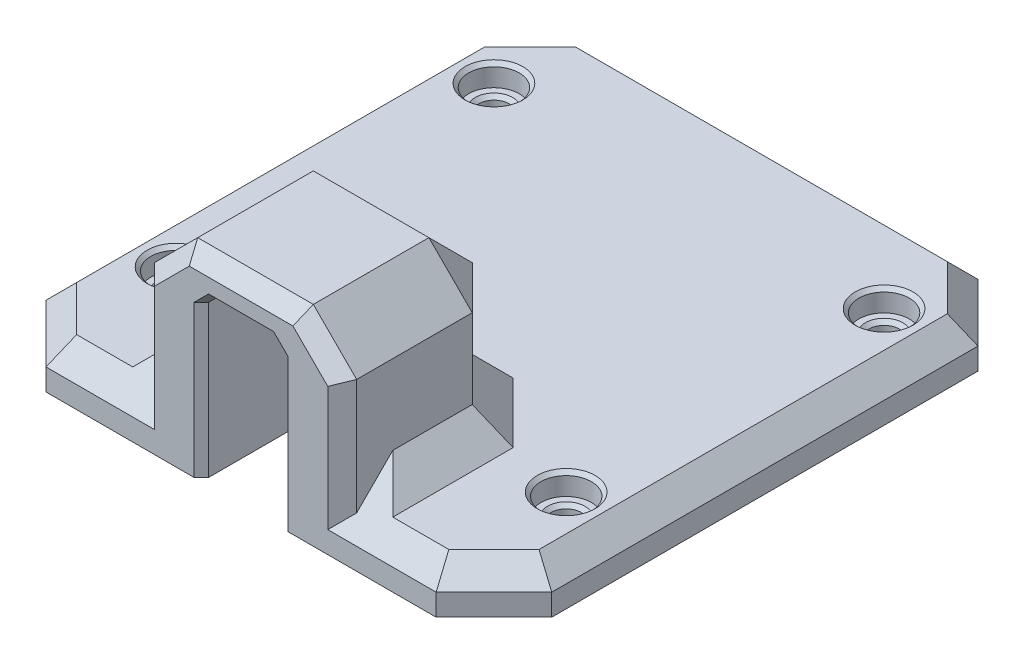
SolidWorks part; units mm, degrees
material "ABS"
ref_plane "Front Plane" through (0, 0, 0) normal (0, 0, 1) x (1, 0, 0)
ref_plane "Top Plane" through (0, 0, 0) normal (0, 1, 0) x (1, 0, 0)
ref_plane "Right Plane" through (0, 0, 0) normal (1, 0, 0) x (0, 0, -1)
sketch "Sketch1" plane through (0, 0, 0) normal (0, 1, 0) x (1, 0, 0)
  line L0 (-35, 27) -> (-27, 35)
  line L1 (-27, 35) -> (27, 35)
  line L2 (-35, 27) -> (-35, -32)
  line L4 (35, 27) -> (35, -32)
  line L5 (27, 35) -> (35, 27)
  line L6 (27, -40) -> (35, -32)
  line L7 (-35, -32) -> (-27, -40)
  line L8 (-1000, 0) -> (49000, 0) construction
  line L9 (0, -1000) -> (0, 49000) construction
  line L11 (-5, -40) -> (-5, -27.65) construction
  line L13 (5, -27.65) -> (5, -40) construction
  line L15 (-5.5, -40) -> (-5.5, -27.8571)
  line L17 (-5.5, -27.8571) -> (-9.5, -23.8571)
  line L18 (-5, -27.65) -> (-9, -23.65) construction
  line L19 (-9, -23.65) -> (-9, -21.15) construction
  line L20 (-9, -21.15) -> (9, -21.15) construction
  line L21 (9, -21.15) -> (9, -23.65) construction
  line L22 (9, -23.65) -> (5, -27.65) construction
  line L23 (-9.5, -23.8571) -> (-9.5, -20.65)
  line L24 (-9.5, -20.65) -> (9.5, -20.65)
  line L25 (9.5, -20.65) -> (9.5, -23.8571)
  line L26 (9.5, -23.8571) -> (5.5, -27.8571)
  line L27 (5.5, -27.8571) -> (5.5, -40)
  line L28 (-27, -40) -> (-5.5, -40)
  line L29 (5.5, -40) -> (27, -40)
  circle A0 centre (-27, 22) radius 2.1
  circle A1 centre (27, 22) radius 2.1
  circle A2 centre (27, -22) radius 2.1
  circle A3 centre (-27, -22) radius 2.1
  point P1 (0, 35)
  point P36 (0, -21.15)
  dimension "D7" = 4.2
  dimension "D1" = 75
  dimension "D2" = 70
  dimension "D3" = 35
  dimension "D4" = 8
  dimension "D5" = 27
  dimension "D6" = 22
  dimension "D8" = 18.85
  dimension "D9" = 18
  dimension "D10" = 4
  dimension "D11" = 2.5
  dimension "D12" = 0.5
extrude "Main Cap Extrude" add sketch "Sketch1" along normal blind 6
chamfer "Main Body Chamfer" distance 3 angle 45 9 edges at (31, 6, 36) (35, 6, 2.5) (31, 6, -31) (0, 6, -35) (-31, 6, -31) (-35, 6, 2.5) (-31, 6, 36) (16.25, 6, 40) (-16.25, 6, 40)
sketch "Sketch4" plane through (0, 6, 0) normal (0, 1, 0) x (1, 0, 0)
  circle A0 centre (-27, 22) radius 3.5
  circle A1 centre (-27, -22) radius 3.5
  circle A2 centre (27, -22) radius 3.5
  circle A3 centre (27, 22) radius 3.5
  dimension "D1" = 7
extrude "Hole Countersink Cut" cut sketch "Sketch4" against normal blind 3
chamfer "Hole Countersink Chamfer" distance 0.5 angle 45 8 edges at (27, 3, -19.9) (27, 3, 24.1) (-27, 3, 24.1) (-27, 3, -19.9) (-27, 6, 25.5) (-27, 6, -18.5) (27, 6, 25.5) (27, 6, -18.5)
sketch "Sketch2" plane through (0, 0, 0) normal (0, 1, 0) x (1, 0, 0)
  line L0 (5.5, -27.8571) -> (5.5, -37) construction
  line L1 (9.5, -23.8571) -> (5.5, -27.8571) construction
  line L2 (9.5, -20.65) -> (9.5, -23.8571) construction
  line L3 (-9.5, -20.65) -> (9.5, -20.65) construction
  line L4 (-9.5, -23.8571) -> (-9.5, -20.65) construction
  line L5 (-5.5, -27.8571) -> (-9.5, -23.8571) construction
  line L6 (-5.5, -37) -> (-5.5, -27.8571) construction
  line L7 (5.5, -27.8571) -> (5.5, -40)
  line L8 (9.5, -23.8571) -> (5.5, -27.8571)
  line L9 (9.5, -20.65) -> (9.5, -23.8571)
  line L10 (-9.5, -20.65) -> (9.5, -20.65)
  line L11 (-9.5, -23.8571) -> (-9.5, -20.65)
  line L12 (-5.5, -27.8571) -> (-9.5, -23.8571)
  line L13 (-5.5, -40) -> (-5.5, -27.8571)
  line L14 (-14, -40) -> (-14, -16)
  line L15 (-27, -40) -> (-5.5, -40) construction
  line L16 (-14, -16) -> (14, -16)
  line L17 (14, -16) -> (14, -40)
  line L18 (5.5, -40) -> (27, -40) construction
  line L19 (14, -40) -> (5.5, -40)
  line L20 (-5.5, -40) -> (-14, -40)
  point P13 (0, 0)
  point P18 (-5.5, -40)
  dimension "D1" = 28
  dimension "D2" = 24
extrude "Main Pinion Chimney Extrude" add sketch "Sketch2" along normal offset from surface (22 mm away) 22 up to face at (0, 0, 15.2955)
sketch "Sketch3" plane through (0, 22, 0) normal (0, 1, 0) x (1, 0, 0)
  line L0 (-14, -16) -> (14, -16)
  line L1 (14, -16) -> (14, -40)
  line L2 (14, -40) -> (-14, -40)
  line L3 (-14, -40) -> (-14, -16)
  point P4 (14, -40)
extrude "Pinion Chimney Cap Extrude" add sketch "Sketch3" along normal blind 5
chamfer "Internal Chimney Chamfer" distance 1 angle 45 10 edges at (9.5, 22, 22.2536) (0, 22, 20.65) (-9.5, 22, 22.2536) (-7.5, 22, 25.8571) (-5.5, 22, 33.9286) (-5.5, 11, 40) (0, 22, 40) (7.5, 22, 25.8571) (5.5, 22, 33.9286) (5.5, 11, 40)
chamfer "Main Chimney External Chamfer" distance 6 angle 45 5 edges at (-14, 27, 28) (14, 27, 28) (-14, 16.5, 16) (14, 16.5, 16) (0, 27, 16)
chamfer "Chimney Plate Chamfer" distance 4 angle 45 5 edges at (14, 6, 29.5) (11, 6, 19) (0, 6, 16) (-11, 6, 19) (-14, 6, 29.5)
chamfer "Chimney Front Chamfer" distance 2 angle 45 5 edges at (14, 12, 40) (11, 24, 40) (0, 27, 40) (-11, 24, 40) (-14, 12, 40)
